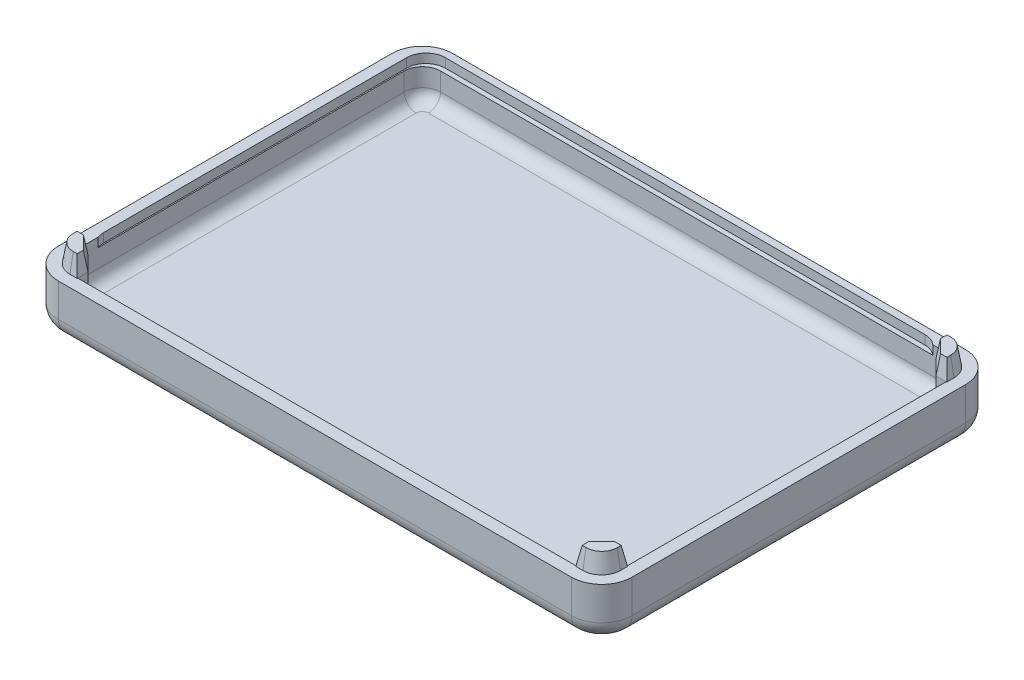
SolidWorks part; units mm, degrees
note: The reader was unsure of these and kept them because the rebuilt part matched: shared geometry of "Sketch1<3>", "Sketch3<2>".
ref_plane "Front Plane" through (0, 0, 0) normal (0, 0, 1) x (1, 0, 0)
ref_plane "Top Plane" through (0, 0, 0) normal (0, 1, 0) x (1, 0, 0)
ref_plane "Right Plane" through (0, 0, 0) normal (1, 0, 0) x (0, 0, -1)
sketch "Sketch1" plane through (0, 0, 0) normal (0, 1, 0) x (1, 0, 0)
  line L0 (-54.4012, 31.9676) -> (30.0988, 31.9676)
  line L1 (-54.4012, -30.9783) -> (30.0988, -30.9783)
  line L2 (-57.4012, -27.9783) -> (-57.4012, 26.9676)
  line L3 (-54.4012, 29.9676) -> (30.0988, 29.9676)
  line L4 (33.0988, -27.9783) -> (33.0988, 26.9676)
  line L5 (-57.4012, -30.9783) -> (33.0988, 29.9676) construction
  line L6 (-57.4012, 29.9676) -> (33.0988, -30.9783) construction
  line L7 (35.0988, -27.9783) -> (35.0988, 26.9676)
  line L8 (-54.4012, -32.9783) -> (30.0988, -32.9783)
  line L9 (-59.4012, -27.9783) -> (-59.4012, 26.9676)
  line L10 (-59.4012, -23.3824) -> (-59.4012, -27.9783) construction
  line L11 (-54.4012, -32.9783) -> (30.0988, -32.9783) construction
  arc A0 (30.0988, 29.9676) -> (33.0988, 26.9676) centre (30.0988, 26.9676) cw
  arc A1 (30.0988, -30.9783) -> (33.0988, -27.9783) centre (30.0988, -27.9783) ccw
  arc A2 (-54.4012, -30.9783) -> (-57.4012, -27.9783) centre (-54.4012, -27.9783) cw
  arc A3 (-57.4012, 26.9676) -> (-54.4012, 29.9676) centre (-54.4012, 26.9676) cw
  arc A4 (30.0988, 31.9676) -> (35.0988, 26.9676) centre (30.0988, 26.9676) cw
  arc A5 (30.0988, -32.9783) -> (35.0988, -27.9783) centre (30.0988, -27.9783) ccw
  arc A6 (-54.4012, -32.9783) -> (-59.4012, -27.9783) centre (-54.4012, -27.9783) cw
  arc A7 (-59.4012, 26.9676) -> (-54.4012, 31.9676) centre (-54.4012, 26.9676) cw
  point P0 (0, 0)
  dimension "D1" = 3
  dimension "D2" = 2
extrude "Boss-Extrude1" add sketch "Sketch1" along normal blind 2 contours L2 A3 L3 A0 L4 A1 L1 A2
extrude "Boss-Extrude2" add sketch "Sketch1<3>" along normal up to surface (8.5 mm away)
sketch "Sketch1<3>" plane through (0, 0, 0) normal (0, 1, 0) x (1, 0, 0) same geometry as "Sketch1"
sketch "Sketch2" plane through (0, 8.5, 0) normal (0, 1, 0) x (1, 0, 0)
  line L0 (27.7988, -25.5324) -> (27.7988, 27.5676)
  line L1 (24.5988, 30.7676) -> (-54.4012, 30.7676)
  line L2 (-57.6012, 27.5676) -> (-57.6012, -22.3324)
  line L3 (-54.4012, -25.5324) -> (27.7988, -25.5324)
  line L4 (24.5988, 30.5676) -> (20.8488, 30.5676) construction
  line L5 (27.5988, 8.1176) -> (27.5988, 27.5676) construction
  line L6 (24.5988, 30.7676) -> (24.5988, 30.5676) construction
  line L7 (-57.4012, 26.9676) -> (-57.4012, -27.9783) construction
  line L8 (-54.4012, -25.3324) -> (24.5988, -25.3324) construction
  arc A0 (27.7988, 27.5676) -> (24.5988, 30.7676) centre (24.5988, 27.5676) ccw
  arc A1 (-54.4012, 30.7676) -> (-57.6012, 27.5676) centre (-54.4012, 27.5676) ccw
  arc A2 (-57.6012, -22.3324) -> (-54.4012, -25.5324) centre (-54.4012, -22.3324) ccw
  point P10 (24.5988, 30.7676)
  point P15 (-57.8049, 27.5676)
  point P16 (-54.6049, -27.4897)
  dimension "D1" = 0.2
  dimension "D2" = 0.2
  dimension "D3" = 0.2
  dimension "D4" = 0.2
extrude "Cut-Extrude1" cut sketch "Sketch2" against normal up to vertex (1.5 mm away)
sketch "Sketch3" plane through (0, 2, 0) normal (0, 1, 0) x (1, 0, 0)
  line L1 (28.932, -29.2864) -> (31.4069, -26.8115)
  line L3 (32.2908, -30.1703) -> (30.1695, -28.049) construction
  line L5 (31.4069, 25.8008) -> (28.932, 28.2757)
  line L8 (-53.2345, -29.2864) -> (-55.7094, -26.8115)
  line L10 (33.1988, -27.9783) -> (33.1988, -26.8115)
  line L11 (33.1988, -26.8115) -> (31.4069, -26.8115)
  line L12 (30.0988, -31.0783) -> (28.932, -31.0783)
  line L13 (28.932, -31.0783) -> (28.932, -29.2864)
  line L14 (28.932, 28.2757) -> (28.932, 30.0676)
  line L15 (28.932, 30.0676) -> (30.0988, 30.0676)
  line L16 (33.1988, 26.9676) -> (33.1988, 25.8008)
  line L17 (33.1988, 25.8008) -> (31.4069, 25.8008)
  line L18 (-54.4012, -31.0783) -> (-53.2345, -31.0783)
  line L19 (-53.2345, -31.0783) -> (-53.2345, -29.2864)
  line L20 (-55.7094, -26.8115) -> (-57.5012, -26.8115)
  line L21 (-57.5012, -26.8115) -> (-57.5012, -27.9783)
  arc A4 (30.0988, -31.0783) -> (33.1988, -27.9783) centre (30.0988, -27.9783) ccw
  arc A5 (30.0988, -30.9783) -> (33.0988, -27.9783) centre (30.0988, -27.9783) ccw construction
  arc A7 (-54.4012, -31.0783) -> (-57.5012, -27.9783) centre (-54.4012, -27.9783) cw
  arc A8 (33.1988, 26.9676) -> (30.0988, 30.0676) centre (30.0988, 26.9676) ccw
  arc A9 (33.0988, 26.9676) -> (30.0988, 29.9676) centre (30.0988, 26.9676) ccw construction
  arc A10 (-57.4012, -27.9783) -> (-54.4012, -30.9783) centre (-54.4012, -27.9783) ccw construction
  point P30 (-53.3851, -29.7528)
  point P40 (-55.3916, -27.6263)
  point P41 (-55.414, -27.6263)
  dimension "D1" = 0.1
  dimension "D2" = 3
  dimension "D3" = 3.5
extrude "Boss-Extrude3" add sketch "Sketch3" along normal up to surface (6.5 mm away) up to face at (-13.4263, 8.5, -1.045)
extrude "Boss-Extrude4" add sketch "Sketch3<2>" along normal blind 3 draft 10 from surface at 6.5
sketch "Sketch3<2>" plane through (0, 2, 0) normal (0, 1, 0) x (1, 0, 0) same geometry as "Sketch3"
fillet "Fillet1" radius 3 8 edges at (-57.9368, 0, 31.5138) (-59.4012, 0, 0.5053) (-57.9368, 0, -30.5031) (-12.1512, 0, -31.9676) (33.6343, 0, -30.5031) (35.0988, 0, 0.5053) (33.6343, 0, 31.5138) (-12.1512, 0, 32.9783)
fillet "Fillet2" radius 2 14 edges at (30.1695, 2, -27.0383) (32.2528, 2, -25.8008) (33.0988, 2, 0.5053) (32.2528, 2, 26.8115) (30.1695, 2, 28.049) (28.932, 2, 30.1323) (-12.1512, 2, 30.9783) (-53.2345, 2, 30.1323) (-54.4719, 2, 28.049) (-56.5553, 2, 26.8115) (-57.4012, 2, -0.078) (-56.5225, 2, -29.0889) (-12.7346, 2, -29.9676) (28.932, 2, -29.1216)
